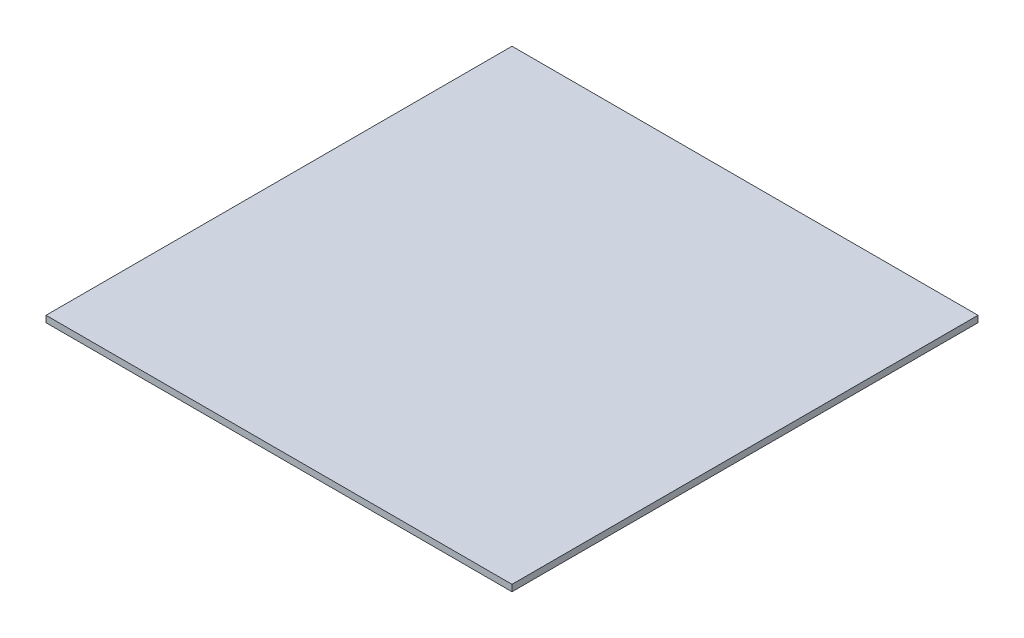
SolidWorks part; units mm, degrees
ref_plane "Front Plane" through (0, 0, 0) normal (0, 0, 1) x (1, 0, 0)
ref_plane "Top Plane" through (0, 0, 0) normal (0, 1, 0) x (1, 0, 0)
ref_plane "Right Plane" through (0, 0, 0) normal (1, 0, 0) x (0, 0, -1)
sketch "Sketch1" plane through (0, 0, 0) normal (0, 1, 0) x (1, 0, 0)
  line L1 (0, 0) -> (457.2, 0)
  line L2 (0, 0) -> (0, 457.2)
  line L3 (0, 457.2) -> (457.2, 457.2)
  line L4 (457.2, 0) -> (457.2, 457.2)
  dimension "D1" = 457.2
  dimension "D2" = 457.2
extrude "Boss-Extrude1" add sketch "Sketch1" along normal blind 6.35
